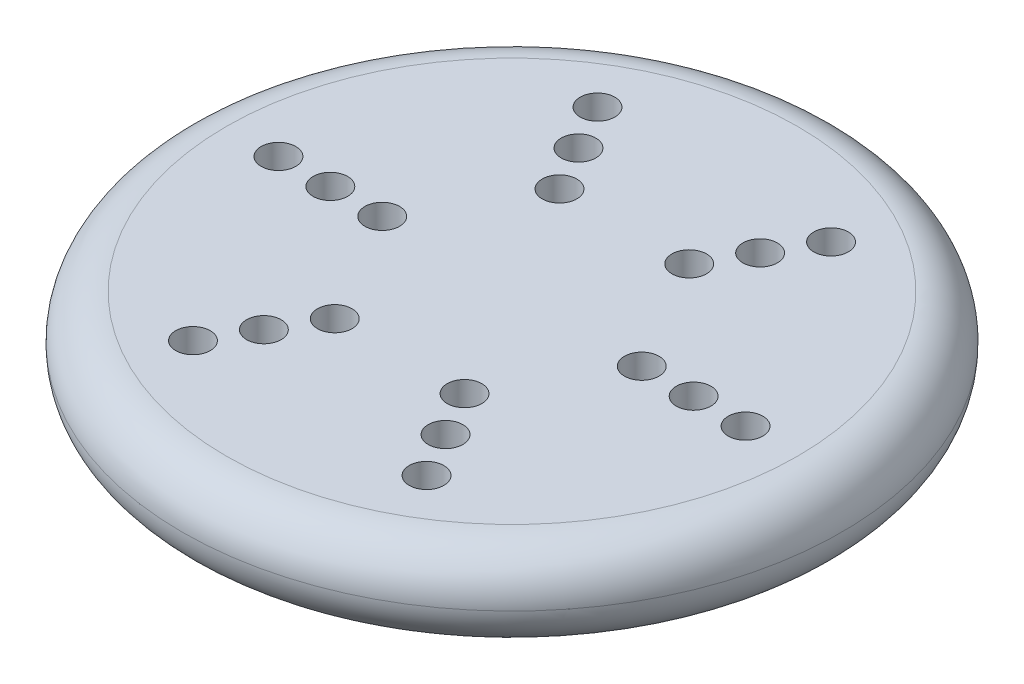
SolidWorks part; units mm, degrees
ref_plane "Front Plane" through (0, 0, 0) normal (0, 0, 1) x (1, 0, 0)
ref_plane "Top Plane" through (0, 0, 0) normal (0, 1, 0) x (1, 0, 0)
ref_plane "Right Plane" through (0, 0, 0) normal (1, 0, 0) x (0, 0, -1)
sketch "Sketch2" plane through (0, 0, 0) normal (0, 1, 0) x (1, 0, 0)
  circle A0 centre (0, 0) radius 19.05
  dimension "D1" = 38.1
extrude "Boss-Extrude1" add sketch "Sketch2" along normal blind 5.08
sketch "Sketch3" plane through (0, 5.08, 0) normal (0, 1, 0) x (1, 0, 0)
  circle A0 centre (-6.75, -11.6913) radius 1 construction
  circle A1 centre (-5.25, -9.0933) radius 1 construction
  circle A2 centre (-3.75, -6.4952) radius 1 construction
  circle A3 centre (-13.5, 0) radius 1 construction
  circle A4 centre (-10.5, 0) radius 1 construction
  circle A5 centre (-7.5, 0) radius 1 construction
  circle A6 centre (-3.75, 6.4952) radius 1 construction
  circle A7 centre (-5.25, 9.0933) radius 1 construction
  circle A8 centre (-6.75, 11.6913) radius 1 construction
  circle A9 centre (6.75, 11.6913) radius 1 construction
  circle A10 centre (5.25, 9.0933) radius 1 construction
  circle A11 centre (3.75, 6.4952) radius 1 construction
  circle A12 centre (13.5, 0) radius 1 construction
  circle A13 centre (10.5, 0) radius 1 construction
  circle A14 centre (7.5, 0) radius 1 construction
  circle A15 centre (3.75, -6.4952) radius 1 construction
  circle A16 centre (5.25, -9.0933) radius 1 construction
  circle A17 centre (6.75, -11.6913) radius 1 construction
  circle A18 centre (-6.75, -11.6913) radius 1
  circle A19 centre (-5.25, -9.0933) radius 1
  circle A20 centre (-3.75, -6.4952) radius 1
  circle A21 centre (-13.5, 0) radius 1
  circle A22 centre (-10.5, 0) radius 1
  circle A23 centre (-7.5, 0) radius 1
  circle A24 centre (-3.75, 6.4952) radius 1
  circle A25 centre (-5.25, 9.0933) radius 1
  circle A26 centre (-6.75, 11.6913) radius 1
  circle A27 centre (6.75, 11.6913) radius 1
  circle A28 centre (5.25, 9.0933) radius 1
  circle A29 centre (3.75, 6.4952) radius 1
  circle A30 centre (13.5, 0) radius 1
  circle A31 centre (10.5, 0) radius 1
  circle A32 centre (7.5, 0) radius 1
  circle A33 centre (3.75, -6.4952) radius 1
  circle A34 centre (5.25, -9.0933) radius 1
  circle A35 centre (6.75, -11.6913) radius 1
extrude "Cut-Extrude1" cut sketch "Sketch3" against normal through all
fillet "Fillet1" radius 2.54 2 edges at (0, 0, 19.05) (0, 5.08, 19.05)
